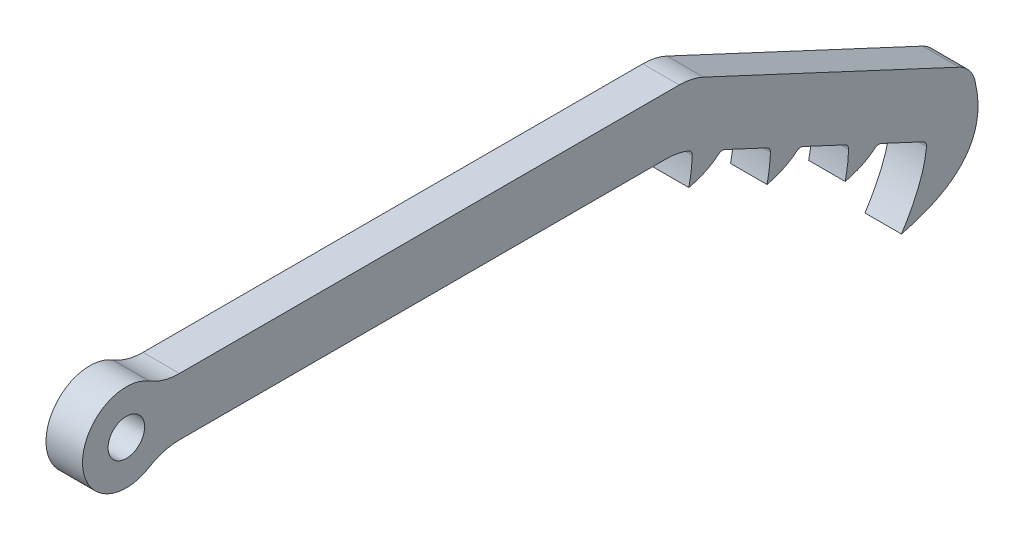
SolidWorks part; units mm, degrees
ref_plane "Front Plane" through (0, 0, 0) normal (0, 0, 1) x (1, 0, 0)
ref_plane "Top Plane" through (0, 0, 0) normal (0, 1, 0) x (1, 0, 0)
ref_plane "Right Plane" through (0, 0, 0) normal (1, 0, 0) x (0, 0, -1)
sketch "Sketch1" plane through (0, 0, 0) normal (1, 0, 0) x (0, 0, -1)
  line L0 (-57.9219, 44.5435) -> (-40.0493, 54.8622)
  line L1 (-40.0493, 49.8622) -> (56.1047, 49.8622)
  line L2 (56.1047, 49.8622) -> (102.5472, 28.2057)
  line L3 (-40.0493, 59.8622) -> (58.3217, 59.8622)
  line L4 (58.3217, 59.8622) -> (106.7734, 37.2688)
  line L5 (56.1047, 49.8622) -> (84.5622, 36.5923) construction
  line L6 (58.3217, 59.8622) -> (88.7883, 45.6554) construction
  line L7 (102.5472, 28.2057) -> (106.7734, 37.2688)
  line L8 (102.5472, 28.2057) -> (111.6103, 23.9795)
  line L9 (93.4842, 32.4319) -> (106.7734, 37.2688)
  circle A0 centre (-57.9219, 44.5435) radius 15.875
  circle A1 centre (-40.0493, 54.8622) radius 4.7625
  circle A2 centre (-40.0493, 54.8622) radius 2.5
  circle A3 centre (-40.0493, 54.8622) radius 5
  circle A4 centre (-40.0493, 54.8622) radius 7.62
  parabola Q0 (106.7734, 37.2688) -> (94.7552, 18.0752) focus (102.5472, 28.2057) apex (107.0788, 26.0926)
  parabola Q1 (99.1632, 29.7837) -> (94.7552, 18.0752) focus (93.4842, 32.4319) apex (98.5101, 34.2612)
  parabola Q2 (93.4202, 43.4955) -> (84.9631, 30.8885) focus (87.9414, 37.2725) apex (91.341, 34.5621)
  parabola Q3 (85.5686, 36.123) -> (84.9631, 30.8885) focus (78.3442, 40.2408) apex (83.762, 43.3694)
  parabola Q4 (79.8256, 49.8348) -> (71.3685, 37.2277) focus (74.3468, 43.6117) apex (77.7464, 40.9013)
  parabola Q5 (71.974, 42.4623) -> (71.3685, 37.2277) focus (64.7496, 46.58) apex (70.1674, 49.7086)
  parabola Q6 (66.2309, 56.1741) -> (57.7739, 43.567) focus (60.7522, 49.951) apex (64.1518, 47.2406)
  parabola Q7 (58.3794, 48.8015) -> (57.7739, 43.567) focus (51.155, 52.9193) apex (56.5728, 56.0479)
  point P12 (93.4842, 32.4319)
  point P19 (100.1288, 34.8504)
  dimension "D1" = 10
  dimension "D2" = 12.4745
  dimension "D3" = 5
  dimension "D4" = 15
extrude "Boss-Extrude1" add sketch "Sketch1" along normal blind 6.35 contours A2 | A2 A1 | A3 A0 A1 | L1 A4 L3 A3 | Q6 L4 L3 A4 L1 L2 | L4 Q6 L2 Q4 | L4 Q4 L2 Q2 | L4 Q2 L2 L9 | L9 L2 L7 | Q0 L7 L8 | L2 Q1 Q0 L8 | L2 Q3 Q2 | L2 Q5 Q4 | L2 Q7 Q6 | A4 | A2 region at (0, 57.2087, 40.6781) region at (0, 53.0598, 44.5079) region at (0, 59.3323, 41.2471) region at (0, 54.8622, 34.7231) region at (0, 54.7054, -16.6549) region at (0, 47.8087, -72.3396) region at (0, 46.1053, -60.0268) region at (0, 41.4694, -85.9342) region at (0, 37.45, -97.3772) region at (0, 39.7661, -73.6214) region at (0, 30.7591, -105.9447) region at (0, 32.6355, -100.9349) region at (0, 33.4268, -87.216) region at (0, 23.9786, -100.9688)
sketch "Sketch2" plane through (6.35, 0, 0) normal (1, 0, 0) x (0, 0, -1)
  arc A0 (-34.2992, 59.8622) -> (-34.2992, 49.8622) centre (-40.0493, 54.8622) ccw construction
  point P0 (-40.0493, 54.8622)
  point P1 (0, 0)
  point P5 (0, 0)
hole_wizard "1/4 (0.2500) Dowel Hole2" positions "Sketch2" profile "Sketch3" hole size "1/4" standard "ANSI Inch" end condition through all
sketch "Sketch3" plane through (6.35, 54.8622, 40.0493) normal (0, 1, 0) x (0, 0, -1)
  line L0 (0, 0) -> (0, 6.35)
  line L1 (0, 6.35) -> (3.175, 6.35)
  line L2 (3.175, 6.35) -> (3.175, 0)
  line L5 (3.175, 0) -> (0, 0)
  line L11 (0, -6.35) -> (0, 107.95) construction
  dimension "Thru Hole Dia." = 6.35
  dimension "Thru Hole Depth" = 6.35
fillet "Fillet1" radius 10 2 edges at (3.175, 59.8622, 34.2992) (3.175, 49.8622, 34.2992)
fillet "Fillet2" radius 10 2 edges at (3.175, 49.8622, -56.1047) (3.175, 59.8622, -58.3217)
fillet "Fillet4" radius 5 1 edges at (3.175, 37.2688, -106.7734)
fillet "Fillet5" radius 1 7 edges at (3.175, 33.7664, -90.6224) (3.175, 40.1057, -77.0278) (3.175, 46.4449, -63.4331) (3.175, 48.8015, -58.3794) (3.175, 42.4623, -71.974) (3.175, 36.123, -85.5686) (3.175, 29.7837, -99.1632)
